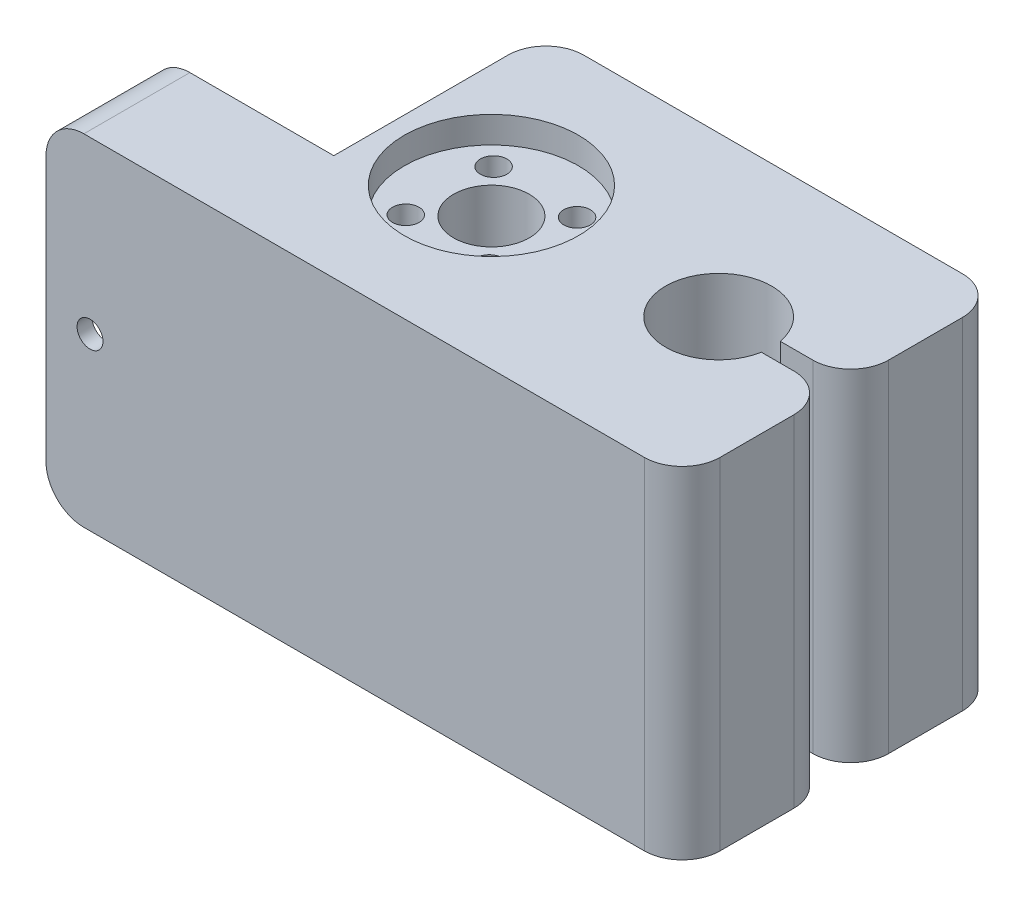
SolidWorks part; units mm, degrees
ref_plane "Front Plane" through (0, 0, 0) normal (0, 0, 1) x (1, 0, 0)
ref_plane "Top Plane" through (0, 0, 0) normal (0, 1, 0) x (1, 0, 0)
ref_plane "Right Plane" through (0, 0, 0) normal (1, 0, 0) x (0, 0, -1)
sketch "Sketch1" plane through (0, 0, 0) normal (0, 0, 1) x (1, 0, 0)
  line L0 (84, 22.5) -> (0, 22.5) construction
  line L1 (0, 0) -> (84, 0)
  line L2 (0, 0) -> (0, 45)
  line L3 (0, 45) -> (84, 45)
  line L4 (84, 0) -> (84, 45)
  dimension "D1" = 84
  dimension "D2" = 45
extrude "Boss-Extrude1" add sketch "Sketch1" along normal blind 42
sketch "Sketch3" plane through (0, 45, 0) normal (0, 1, 0) x (1, 0, 0)
  line L0 (0, -28) -> (24, -28)
  line L1 (0, -42) -> (0, 0) construction
  line L2 (24, -28) -> (24, 0)
  line L3 (84, 0) -> (0, 0) construction
  line L4 (24, 0) -> (0, 0)
  line L5 (0, 0) -> (0, -28)
  dimension "D1" = 28
  dimension "D2" = 24
extrude "Cut-Extrude2" cut sketch "Sketch3" against normal through all
sketch "Sketch4" plane through (0, 0, 0) normal (-1, 0, 0) x (0, 0, 1)
  line L0 (42, 45) -> (42, 0) construction
  line L1 (30, 31) -> (40, 31)
  line L2 (30, 31) -> (30, 14)
  line L3 (30, 14) -> (40, 14)
  line L4 (40, 31) -> (40, 14)
  line L5 (28, 0) -> (28, 45) construction
  line L6 (42, 45) -> (28, 45) construction
  dimension "D1" = 17
  dimension "D2" = 2
  dimension "D3" = 2
  dimension "D4" = 14
extrude "Cut-Extrude3" cut sketch "Sketch4" against normal blind 26
sketch "Sketch7" plane through (0, 45, 0) normal (0, 1, 0) x (1, 0, 0)
  circle A0 centre (37.8131, -21) radius 11.5
extrude "Cut-Extrude5" cut sketch "Sketch7" against normal blind 3.5 contours A0
sketch "Sketch11" plane through (0, 41.5, 0) normal (0, 1, 0) x (1, 0, 0)
  circle A0 centre (32.0148, -26.5117) radius 1.75
  circle A1 centre (32.3014, -15.2016) radius 1.75
  circle A2 centre (43.6115, -15.4883) radius 1.75
  circle A3 centre (43.3248, -26.7984) radius 1.75
extrude "Cut-Extrude6" cut sketch "Sketch11" against normal blind 10
sketch "Sketch12" plane through (0, 41.5, 0) normal (0, 1, 0) x (1, 0, 0)
  circle A0 centre (37.8131, -21) radius 5
extrude "Cut-Extrude7" cut sketch "Sketch12" against normal through all contours A0
sketch "Sketch13" plane through (0, 45, 0) normal (0, 1, 0) x (1, 0, 0)
  circle A0 centre (67.8131, -21) radius 7
extrude "Cut-Extrude8" cut sketch "Sketch13" against normal through all
sketch "Sketch14" plane through (0, 45, 0) normal (0, 1, 0) x (1, 0, 0)
  line L0 (67.8131, -21) -> (84, -21) construction
  line L1 (84, -42) -> (84, 0) construction
  line L3 (63.307, -22.25) -> (84, -22.25)
  line L4 (63.307, -22.25) -> (63.307, -19.75)
  line L5 (63.307, -19.75) -> (84, -19.75)
  line L6 (84, -22.25) -> (84, -19.75)
  line L7 (63.307, -22.25) -> (84, -19.75) construction
  line L8 (63.307, -19.75) -> (84, -22.25) construction
  point P5 (73.6535, -21)
  dimension "D1" = 2.5
extrude "Cut-Extrude9" cut sketch "Sketch14" against normal through all
fillet "Fillet2" radius 5 7 edges at (24, 22.5, 0) (84, 22.5, 0) (84, 22.5, 42) (0, 0, 35) (0, 45, 35) (84, 22.5, 22.25) (84, 22.5, 19.75)
sketch "Sketch15" plane through (0, 0, 42) normal (0, 0, 1) x (1, 0, 0)
  circle A0 centre (5.8131, 22.5) radius 1.7123
extrude "Cut-Extrude10" cut sketch "Sketch15" against normal through all
